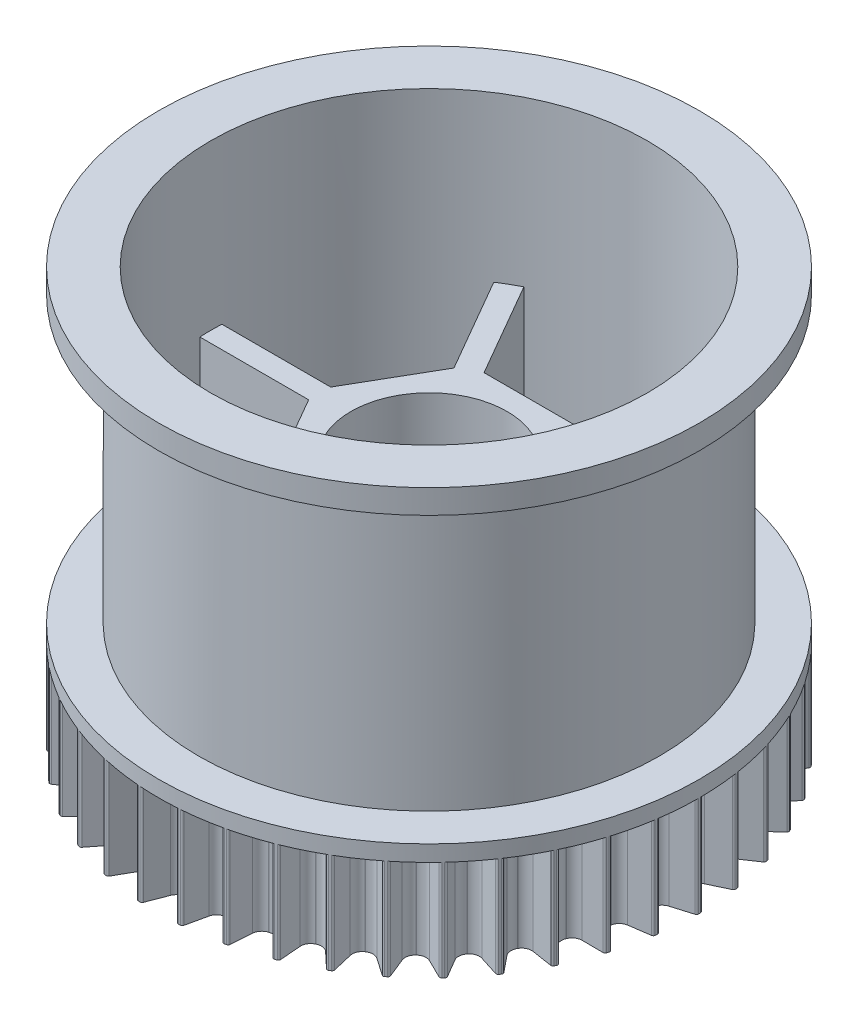
SolidWorks part; units mm, degrees
ref_plane "前视基准面" through (0, 0, 0) normal (0, 0, 1) x (1, 0, 0)
ref_plane "上视基准面" through (0, 0, 0) normal (0, 1, 0) x (1, 0, 0)
ref_plane "右视基准面" through (0, 0, 0) normal (1, 0, 0) x (0, 0, -1)
other "Configuration Table"
sketch "草图1" plane through (0, 0, 0) normal (0, 1, 0) x (1, 0, 0)
  line L0 (0, 0) -> (7.9279, 0) construction
  line L1 (0, 0) -> (0, 4.4256) construction
  line L2 (12.4216, 0.4494) -> (13.4287, 0.1463)
  line L3 (12.4216, -0.4494) -> (13.4287, -0.1463)
  line L4 (12.2159, -2.2957) -> (13.2569, -2.1461)
  line L5 (12.3499, -1.407) -> (13.3005, -1.8568)
  line L6 (11.7373, -4.0908) -> (12.789, -4.098)
  line L7 (12.0023, -3.2319) -> (12.8752, -3.8184)
  line L8 (10.9965, -5.7945) -> (12.0354, -5.9583)
  line L9 (11.3865, -4.9846) -> (12.1623, -5.6947)
  line L10 (10.0101, -7.3687) -> (11.0129, -7.6855)
  line L11 (10.5164, -6.626) -> (11.1777, -7.4438)
  line L12 (8.8, -8.7783) -> (9.7445, -9.2411)
  line L13 (9.4114, -8.1194) -> (9.9434, -9.0266)
  line L14 (7.3934, -9.9918) -> (8.2583, -10.5902)
  line L15 (8.0961, -9.4314) -> (8.487, -10.4078)
  line L16 (5.8216, -10.9822) -> (6.5877, -11.7028)
  line L17 (6.6, -10.5328) -> (6.841, -11.5565)
  line L18 (4.1198, -11.7272) -> (4.7699, -12.5539)
  line L19 (4.9565, -11.3988) -> (5.0422, -12.447)
  line L20 (2.3259, -12.2102) -> (2.8456, -13.1246)
  line L21 (3.2022, -12.0102) -> (3.1308, -13.0595)
  line L22 (0.4801, -12.4205) -> (0.8577, -13.4021)
  line L23 (1.3764, -12.3533) -> (1.1494, -13.3802)
  line L24 (-1.3764, -12.3533) -> (-1.1494, -13.3802)
  line L25 (-0.4801, -12.4205) -> (-0.8577, -13.4021)
  line L26 (-3.2022, -12.0102) -> (-3.1308, -13.0595)
  line L27 (-2.3259, -12.2102) -> (-2.8456, -13.1246)
  line L28 (-4.9565, -11.3988) -> (-5.0422, -12.447)
  line L29 (-4.1198, -11.7272) -> (-4.7699, -12.5539)
  line L30 (-6.6, -10.5328) -> (-6.841, -11.5565)
  line L31 (-5.8216, -10.9822) -> (-6.5877, -11.7028)
  line L32 (-8.0961, -9.4314) -> (-8.487, -10.4078)
  line L33 (-7.3934, -9.9918) -> (-8.2583, -10.5902)
  line L34 (-9.4114, -8.1194) -> (-9.9434, -9.0266)
  line L35 (-8.8, -8.7783) -> (-9.7445, -9.2411)
  line L36 (-10.5164, -6.626) -> (-11.1777, -7.4438)
  line L37 (-10.0101, -7.3687) -> (-11.0129, -7.6855)
  line L38 (-11.3865, -4.9846) -> (-12.1623, -5.6947)
  line L39 (-10.9965, -5.7945) -> (-12.0354, -5.9583)
  line L40 (-12.0023, -3.2319) -> (-12.8752, -3.8184)
  line L41 (-11.7373, -4.0908) -> (-12.789, -4.098)
  line L42 (-12.3499, -1.407) -> (-13.3005, -1.8568)
  line L43 (-12.2159, -2.2957) -> (-13.2569, -2.1461)
  line L44 (-12.4216, 0.4494) -> (-13.4287, 0.1463)
  line L45 (-12.4216, -0.4494) -> (-13.4287, -0.1463)
  line L46 (-12.2159, 2.2957) -> (-13.2569, 2.1461)
  line L47 (-12.3499, 1.407) -> (-13.3005, 1.8568)
  line L48 (-11.7373, 4.0908) -> (-12.789, 4.098)
  line L49 (-12.0023, 3.2319) -> (-12.8752, 3.8184)
  line L50 (-10.9965, 5.7945) -> (-12.0354, 5.9583)
  line L51 (-11.3865, 4.9846) -> (-12.1623, 5.6947)
  line L52 (-10.0101, 7.3687) -> (-11.0129, 7.6855)
  line L53 (-10.5164, 6.626) -> (-11.1777, 7.4438)
  line L54 (-8.8, 8.7783) -> (-9.7445, 9.2411)
  line L55 (-9.4114, 8.1194) -> (-9.9434, 9.0266)
  line L56 (-7.3934, 9.9918) -> (-8.2583, 10.5902)
  line L57 (-8.0961, 9.4314) -> (-8.487, 10.4078)
  line L58 (-5.8216, 10.9822) -> (-6.5877, 11.7028)
  line L59 (-6.6, 10.5328) -> (-6.841, 11.5565)
  line L60 (-4.1198, 11.7272) -> (-4.7699, 12.5539)
  line L61 (-4.9565, 11.3988) -> (-5.0422, 12.447)
  line L62 (-2.3259, 12.2102) -> (-2.8456, 13.1246)
  line L63 (-3.2022, 12.0102) -> (-3.1308, 13.0595)
  line L64 (-0.4801, 12.4205) -> (-0.8577, 13.4021)
  line L65 (-1.3764, 12.3533) -> (-1.1494, 13.3802)
  line L66 (1.3764, 12.3533) -> (1.1494, 13.3802)
  line L67 (0.4801, 12.4205) -> (0.8577, 13.4021)
  line L68 (3.2022, 12.0102) -> (3.1308, 13.0595)
  line L69 (2.3259, 12.2102) -> (2.8456, 13.1246)
  line L70 (4.9565, 11.3988) -> (5.0422, 12.447)
  line L71 (4.1198, 11.7272) -> (4.7699, 12.5539)
  line L72 (6.6, 10.5328) -> (6.841, 11.5565)
  line L73 (5.8216, 10.9822) -> (6.5877, 11.7028)
  line L74 (8.0961, 9.4314) -> (8.487, 10.4078)
  line L75 (7.3934, 9.9918) -> (8.2583, 10.5902)
  line L76 (9.4114, 8.1194) -> (9.9434, 9.0266)
  line L77 (8.8, 8.7783) -> (9.7445, 9.2411)
  line L78 (10.5164, 6.626) -> (11.1777, 7.4438)
  line L79 (10.0101, 7.3687) -> (11.0129, 7.6855)
  line L80 (11.3865, 4.9846) -> (12.1623, 5.6947)
  line L81 (10.9965, 5.7945) -> (12.0354, 5.9583)
  line L82 (12.0023, 3.2319) -> (12.8752, 3.8184)
  line L83 (11.7373, 4.0908) -> (12.789, 4.098)
  line L84 (12.3499, 1.407) -> (13.3005, 1.8568)
  line L85 (12.2159, 2.2957) -> (13.2569, 2.1461)
  line L95 (2.8868, 5) -> (-2.8868, 5) construction
  line L96 (2.8868, 5) -> (5.456, 0.55) construction
  line L97 (0, 0) -> (2.8868, 5) construction
  line L98 (-2.8868, 5) -> (-5.456, 0.55) construction
  line L99 (3.2043, -4.45) -> (5.456, -0.55)
  line L100 (2.2517, -5) -> (-2.2517, -5)
  line L101 (-3.2043, -4.45) -> (-5.456, -0.55)
  line L102 (8.1752, 0) -> (11.2, 0) construction
  line L103 (5.456, 0.55) -> (11.1865, 0.55)
  line L104 (5.456, -0.55) -> (11.1865, -0.55)
  line L105 (3.2043, -4.45) -> (6.0696, -9.4128)
  line L106 (2.2517, -5) -> (5.1169, -9.9628)
  line L107 (-2.2517, -5) -> (-5.1169, -9.9628)
  line L108 (-3.2043, -4.45) -> (-6.0696, -9.4128)
  line L109 (-5.456, -0.55) -> (-11.1865, -0.55)
  line L110 (-5.456, 0.55) -> (-11.1865, 0.55)
  line L111 (-3.2043, 4.45) -> (-6.0696, 9.4128)
  line L112 (-2.2517, 5) -> (-5.1169, 9.9628)
  line L113 (2.2517, 5) -> (5.1169, 9.9628)
  line L114 (3.2043, 4.45) -> (6.0696, 9.4128)
  line L115 (0, 0) -> (12.0337, 1.2648) construction
  line L116 (12.0337, -1.2648) -> (0, 0) construction
  line L117 (-5.456, 0.55) -> (-3.2043, 4.45)
  line L118 (-2.2517, 5) -> (2.2517, 5)
  line L119 (3.2043, 4.45) -> (5.456, 0.55)
  circle A0 centre (0, 0) radius 11.2 construction
  circle A1 centre (0, 0) radius 12.1 construction
  circle A2 centre (0, 0) radius 13.5 construction
  arc A3 (13.4999, 0.0509) -> (13.4999, -0.0509) centre (0, 0) cw
  arc A4 (12.0671, 0.8914) -> (12.0337, 1.2648) centre (0, 0) ccw construction
  arc A5 (13.4287, -0.1463) -> (13.4999, -0.0509) centre (13.3999, -0.0505) ccw
  arc A6 (13.4287, 0.1463) -> (13.4999, 0.0509) centre (13.3999, 0.0505) cw
  arc A7 (12.0671, -0.8914) -> (12.0337, -1.2648) centre (0, 0) cw construction
  arc A8 (12.4216, -0.4494) -> (12.0671, -0.8914) centre (12.5658, -0.9282) ccw
  arc A9 (12.4216, 0.4494) -> (12.0671, 0.8914) centre (12.5658, 0.9282) cw
  arc A10 (12.2159, -2.2957) -> (11.7995, -2.6799) centre (12.2871, -2.7907) ccw
  arc A11 (12.3499, -1.407) -> (12.0652, -0.9171) centre (12.5638, -0.955) cw
  arc A12 (13.3005, -1.8568) -> (13.3567, -1.9617) centre (13.2578, -1.9472) cw
  arc A13 (13.3567, -1.9617) -> (13.3415, -2.0624) centre (0, 0) cw
  arc A14 (13.2569, -2.1461) -> (13.3415, -2.0624) centre (13.2427, -2.0471) ccw
  arc A15 (11.7373, -4.0908) -> (11.2683, -4.4086) centre (11.7339, -4.5908) ccw
  arc A16 (12.0023, -3.2319) -> (11.7937, -2.7051) centre (12.2811, -2.8169) cw
  arc A17 (12.8752, -3.8184) -> (12.9151, -3.9305) centre (12.8195, -3.9014) cw
  arc A18 (12.9151, -3.9305) -> (12.8851, -4.0278) centre (0, 0) cw
  arc A19 (12.789, -4.098) -> (12.8851, -4.0278) centre (12.7897, -3.998) ccw
  arc A20 (10.9965, -5.7945) -> (10.4854, -6.0388) centre (10.9186, -6.2884) ccw
  arc A21 (11.3865, -4.9846) -> (11.2589, -4.4326) centre (11.7241, -4.6158) cw
  arc A22 (12.1623, -5.6947) -> (12.1851, -5.8115) centre (12.0948, -5.7685) cw
  arc A23 (12.1851, -5.8115) -> (12.1409, -5.9032) centre (0, 0) cw
  arc A24 (12.0354, -5.9583) -> (12.1409, -5.9032) centre (12.051, -5.8595) ccw
  arc A25 (10.0101, -7.3687) -> (9.4682, -7.5341) centre (9.8595, -7.8455) ccw
  arc A26 (10.5164, -6.626) -> (10.4724, -6.0612) centre (10.9052, -6.3116) cw
  arc A27 (11.1777, -7.4438) -> (11.1828, -7.5627) centre (11.1, -7.5067) cw
  arc A28 (11.1828, -7.5627) -> (11.1255, -7.6468) centre (0, 0) cw
  arc A29 (11.0129, -7.6855) -> (11.1255, -7.6468) centre (11.0431, -7.5902) ccw
  arc A30 (8.8, -8.7783) -> (8.2395, -8.8611) centre (8.58, -9.2273) ccw
  arc A31 (9.4114, -8.1194) -> (9.4521, -7.5543) centre (9.8427, -7.8665) cw
  arc A32 (9.9434, -9.0266) -> (9.9308, -9.145) centre (9.8572, -9.0772) cw
  arc A33 (9.9308, -9.145) -> (9.8615, -9.2196) centre (0, 0) cw
  arc A34 (9.7445, -9.2411) -> (9.8615, -9.2196) centre (9.7885, -9.1513) ccw
  arc A35 (7.3934, -9.9918) -> (6.8268, -9.9902) centre (7.1089, -10.403) ccw
  arc A36 (8.0961, -9.4314) -> (8.2206, -8.8787) centre (8.5603, -9.2456) cw
  arc A37 (8.487, -10.4078) -> (8.4568, -10.5229) centre (8.3942, -10.445) cw
  arc A38 (8.4568, -10.5229) -> (8.3773, -10.5864) centre (0, 0) cw
  arc A39 (8.2583, -10.5902) -> (8.3773, -10.5864) centre (8.3152, -10.508) ccw
  arc A40 (5.8216, -10.9822) -> (5.2616, -10.8961) centre (5.479, -11.3464) ccw
  arc A41 (6.6, -10.5328) -> (6.8055, -10.0048) centre (7.0867, -10.4182) cw
  arc A42 (6.841, -11.5565) -> (6.794, -11.6658) centre (6.7437, -11.5794) cw
  arc A43 (6.794, -11.6658) -> (6.7059, -11.7167) centre (0, 0) cw
  arc A44 (6.5877, -11.7028) -> (6.7059, -11.7167) centre (6.6562, -11.6299) ccw
  arc A45 (4.1198, -11.7272) -> (3.5789, -11.5586) centre (3.7268, -12.0362) ccw
  arc A46 (4.9565, -11.3988) -> (5.2384, -10.9073) centre (5.4548, -11.358) cw
  arc A47 (5.0422, -12.447) -> (4.9795, -12.5481) centre (4.9426, -12.4552) cw
  arc A48 (4.9795, -12.5481) -> (4.8847, -12.5853) centre (0, 0) cw
  arc A49 (4.7699, -12.5539) -> (4.8847, -12.5853) centre (4.8485, -12.4921) ccw
  arc A50 (2.3259, -12.2102) -> (1.8162, -11.9629) centre (1.8912, -12.4573) ccw
  arc A51 (3.2022, -12.0102) -> (3.5542, -11.5662) centre (3.7011, -12.0442) cw
  arc A52 (3.1308, -13.0595) -> (3.0536, -13.1501) centre (3.031, -13.0527) cw
  arc A53 (3.0536, -13.1501) -> (2.9544, -13.1728) centre (0, 0) cw
  arc A54 (2.8456, -13.1246) -> (2.9544, -13.1728) centre (2.9325, -13.0752) ccw
  arc A55 (0.4801, -12.4205) -> (0.0129, -12.1) centre (0.0134, -12.6) ccw
  arc A56 (1.3764, -12.3533) -> (1.7906, -11.9668) centre (1.8646, -12.4613) cw
  arc A57 (1.1494, -13.3802) -> (1.0596, -13.4584) centre (1.0518, -13.3587) cw
  arc A58 (1.0596, -13.4584) -> (0.9581, -13.466) centre (0, 0) cw
  arc A59 (0.8577, -13.4021) -> (0.9581, -13.466) centre (0.951, -13.3662) ccw
  arc A60 (-1.3764, -12.3533) -> (-1.7906, -11.9668) centre (-1.8646, -12.4613) ccw
  arc A61 (-0.4801, -12.4205) -> (-0.0129, -12.1) centre (-0.0134, -12.6) cw
  arc A62 (-0.8577, -13.4021) -> (-0.9581, -13.466) centre (-0.951, -13.3662) cw
  arc A63 (-0.9581, -13.466) -> (-1.0596, -13.4584) centre (0, 0) cw
  arc A64 (-1.1494, -13.3802) -> (-1.0596, -13.4584) centre (-1.0518, -13.3587) ccw
  arc A65 (-3.2022, -12.0102) -> (-3.5542, -11.5662) centre (-3.7011, -12.0442) ccw
  arc A66 (-2.3259, -12.2102) -> (-1.8162, -11.9629) centre (-1.8912, -12.4573) cw
  arc A67 (-2.8456, -13.1246) -> (-2.9544, -13.1728) centre (-2.9325, -13.0752) cw
  arc A68 (-2.9544, -13.1728) -> (-3.0536, -13.1501) centre (0, 0) cw
  arc A69 (-3.1308, -13.0595) -> (-3.0536, -13.1501) centre (-3.031, -13.0527) ccw
  arc A70 (-4.9565, -11.3988) -> (-5.2384, -10.9073) centre (-5.4548, -11.358) ccw
  arc A71 (-4.1198, -11.7272) -> (-3.5789, -11.5586) centre (-3.7268, -12.0362) cw
  arc A72 (-4.7699, -12.5539) -> (-4.8847, -12.5853) centre (-4.8485, -12.4921) cw
  arc A73 (-4.8847, -12.5853) -> (-4.9795, -12.5481) centre (0, 0) cw
  arc A74 (-5.0422, -12.447) -> (-4.9795, -12.5481) centre (-4.9426, -12.4552) ccw
  arc A75 (-6.6, -10.5328) -> (-6.8055, -10.0048) centre (-7.0867, -10.4182) ccw
  arc A76 (-5.8216, -10.9822) -> (-5.2616, -10.8961) centre (-5.479, -11.3464) cw
  arc A77 (-6.5877, -11.7028) -> (-6.7059, -11.7167) centre (-6.6562, -11.6299) cw
  arc A78 (-6.7059, -11.7167) -> (-6.794, -11.6658) centre (0, 0) cw
  arc A79 (-6.841, -11.5565) -> (-6.794, -11.6658) centre (-6.7437, -11.5794) ccw
  arc A80 (-8.0961, -9.4314) -> (-8.2206, -8.8787) centre (-8.5603, -9.2456) ccw
  arc A81 (-7.3934, -9.9918) -> (-6.8268, -9.9902) centre (-7.1089, -10.403) cw
  arc A82 (-8.2583, -10.5902) -> (-8.3773, -10.5864) centre (-8.3152, -10.508) cw
  arc A83 (-8.3773, -10.5864) -> (-8.4568, -10.5229) centre (0, 0) cw
  arc A84 (-8.487, -10.4078) -> (-8.4568, -10.5229) centre (-8.3942, -10.445) ccw
  arc A85 (-9.4114, -8.1194) -> (-9.4521, -7.5543) centre (-9.8427, -7.8665) ccw
  arc A86 (-8.8, -8.7783) -> (-8.2395, -8.8611) centre (-8.58, -9.2273) cw
  arc A87 (-9.7445, -9.2411) -> (-9.8615, -9.2196) centre (-9.7885, -9.1513) cw
  arc A88 (-9.8615, -9.2196) -> (-9.9308, -9.145) centre (0, 0) cw
  arc A89 (-9.9434, -9.0266) -> (-9.9308, -9.145) centre (-9.8572, -9.0772) ccw
  arc A90 (-10.5164, -6.626) -> (-10.4724, -6.0612) centre (-10.9052, -6.3116) ccw
  arc A91 (-10.0101, -7.3687) -> (-9.4682, -7.5341) centre (-9.8595, -7.8455) cw
  arc A92 (-11.0129, -7.6855) -> (-11.1255, -7.6468) centre (-11.0431, -7.5902) cw
  arc A93 (-11.1255, -7.6468) -> (-11.1828, -7.5627) centre (0, 0) cw
  arc A94 (-11.1777, -7.4438) -> (-11.1828, -7.5627) centre (-11.1, -7.5067) ccw
  arc A95 (-11.3865, -4.9846) -> (-11.2589, -4.4326) centre (-11.7241, -4.6158) ccw
  arc A96 (-10.9965, -5.7945) -> (-10.4854, -6.0388) centre (-10.9186, -6.2884) cw
  arc A97 (-12.0354, -5.9583) -> (-12.1409, -5.9032) centre (-12.051, -5.8595) cw
  arc A98 (-12.1409, -5.9032) -> (-12.1851, -5.8115) centre (0, 0) cw
  arc A99 (-12.1623, -5.6947) -> (-12.1851, -5.8115) centre (-12.0948, -5.7685) ccw
  arc A100 (-12.0023, -3.2319) -> (-11.7937, -2.7051) centre (-12.2811, -2.8169) ccw
  arc A101 (-11.7373, -4.0908) -> (-11.2683, -4.4086) centre (-11.7339, -4.5908) cw
  arc A102 (-12.789, -4.098) -> (-12.8851, -4.0278) centre (-12.7897, -3.998) cw
  arc A103 (-12.8851, -4.0278) -> (-12.9151, -3.9305) centre (0, 0) cw
  arc A104 (-12.8752, -3.8184) -> (-12.9151, -3.9305) centre (-12.8195, -3.9014) ccw
  arc A105 (-12.3499, -1.407) -> (-12.0652, -0.9171) centre (-12.5638, -0.955) ccw
  arc A106 (-12.2159, -2.2957) -> (-11.7995, -2.6799) centre (-12.2871, -2.7907) cw
  arc A107 (-13.2569, -2.1461) -> (-13.3415, -2.0624) centre (-13.2427, -2.0471) cw
  arc A108 (-13.3415, -2.0624) -> (-13.3567, -1.9617) centre (0, 0) cw
  arc A109 (-13.3005, -1.8568) -> (-13.3567, -1.9617) centre (-13.2578, -1.9472) ccw
  arc A110 (-12.4216, 0.4494) -> (-12.0671, 0.8914) centre (-12.5658, 0.9282) ccw
  arc A111 (-12.4216, -0.4494) -> (-12.0671, -0.8914) centre (-12.5658, -0.9282) cw
  arc A112 (-13.4287, -0.1463) -> (-13.4999, -0.0509) centre (-13.3999, -0.0505) cw
  arc A113 (-13.4999, -0.0509) -> (-13.4999, 0.0509) centre (0, 0) cw
  arc A114 (-13.4287, 0.1463) -> (-13.4999, 0.0509) centre (-13.3999, 0.0505) ccw
  arc A115 (-12.2159, 2.2957) -> (-11.7995, 2.6799) centre (-12.2871, 2.7907) ccw
  arc A116 (-12.3499, 1.407) -> (-12.0652, 0.9171) centre (-12.5638, 0.955) cw
  arc A117 (-13.3005, 1.8568) -> (-13.3567, 1.9617) centre (-13.2578, 1.9472) cw
  arc A118 (-13.3567, 1.9617) -> (-13.3415, 2.0624) centre (0, 0) cw
  arc A119 (-13.2569, 2.1461) -> (-13.3415, 2.0624) centre (-13.2427, 2.0471) ccw
  arc A120 (-11.7373, 4.0908) -> (-11.2683, 4.4086) centre (-11.7339, 4.5908) ccw
  arc A121 (-12.0023, 3.2319) -> (-11.7937, 2.7051) centre (-12.2811, 2.8169) cw
  arc A122 (-12.8752, 3.8184) -> (-12.9151, 3.9305) centre (-12.8195, 3.9014) cw
  arc A123 (-12.9151, 3.9305) -> (-12.8851, 4.0278) centre (0, 0) cw
  arc A124 (-12.789, 4.098) -> (-12.8851, 4.0278) centre (-12.7897, 3.998) ccw
  arc A125 (-10.9965, 5.7945) -> (-10.4854, 6.0388) centre (-10.9186, 6.2884) ccw
  arc A126 (-11.3865, 4.9846) -> (-11.2589, 4.4326) centre (-11.7241, 4.6158) cw
  arc A127 (-12.1623, 5.6947) -> (-12.1851, 5.8115) centre (-12.0948, 5.7685) cw
  arc A128 (-12.1851, 5.8115) -> (-12.1409, 5.9032) centre (0, 0) cw
  arc A129 (-12.0354, 5.9583) -> (-12.1409, 5.9032) centre (-12.051, 5.8595) ccw
  arc A130 (-10.0101, 7.3687) -> (-9.4682, 7.5341) centre (-9.8595, 7.8455) ccw
  arc A131 (-10.5164, 6.626) -> (-10.4724, 6.0612) centre (-10.9052, 6.3116) cw
  arc A132 (-11.1777, 7.4438) -> (-11.1828, 7.5627) centre (-11.1, 7.5067) cw
  arc A133 (-11.1828, 7.5627) -> (-11.1255, 7.6468) centre (0, 0) cw
  arc A134 (-11.0129, 7.6855) -> (-11.1255, 7.6468) centre (-11.0431, 7.5902) ccw
  arc A135 (-8.8, 8.7783) -> (-8.2395, 8.8611) centre (-8.58, 9.2273) ccw
  arc A136 (-9.4114, 8.1194) -> (-9.4521, 7.5543) centre (-9.8427, 7.8665) cw
  arc A137 (-9.9434, 9.0266) -> (-9.9308, 9.145) centre (-9.8572, 9.0772) cw
  arc A138 (-9.9308, 9.145) -> (-9.8615, 9.2196) centre (0, 0) cw
  arc A139 (-9.7445, 9.2411) -> (-9.8615, 9.2196) centre (-9.7885, 9.1513) ccw
  arc A140 (-7.3934, 9.9918) -> (-6.8268, 9.9902) centre (-7.1089, 10.403) ccw
  arc A141 (-8.0961, 9.4314) -> (-8.2206, 8.8787) centre (-8.5603, 9.2456) cw
  arc A142 (-8.487, 10.4078) -> (-8.4568, 10.5229) centre (-8.3942, 10.445) cw
  arc A143 (-8.4568, 10.5229) -> (-8.3773, 10.5864) centre (0, 0) cw
  arc A144 (-8.2583, 10.5902) -> (-8.3773, 10.5864) centre (-8.3152, 10.508) ccw
  arc A145 (-5.8216, 10.9822) -> (-5.2616, 10.8961) centre (-5.479, 11.3464) ccw
  arc A146 (-6.6, 10.5328) -> (-6.8055, 10.0048) centre (-7.0867, 10.4182) cw
  arc A147 (-6.841, 11.5565) -> (-6.794, 11.6658) centre (-6.7437, 11.5794) cw
  arc A148 (-6.794, 11.6658) -> (-6.7059, 11.7167) centre (0, 0) cw
  arc A149 (-6.5877, 11.7028) -> (-6.7059, 11.7167) centre (-6.6562, 11.6299) ccw
  arc A150 (-4.1198, 11.7272) -> (-3.5789, 11.5586) centre (-3.7268, 12.0362) ccw
  arc A151 (-4.9565, 11.3988) -> (-5.2384, 10.9073) centre (-5.4548, 11.358) cw
  arc A152 (-5.0422, 12.447) -> (-4.9795, 12.5481) centre (-4.9426, 12.4552) cw
  arc A153 (-4.9795, 12.5481) -> (-4.8847, 12.5853) centre (0, 0) cw
  arc A154 (-4.7699, 12.5539) -> (-4.8847, 12.5853) centre (-4.8485, 12.4921) ccw
  arc A155 (-2.3259, 12.2102) -> (-1.8162, 11.9629) centre (-1.8912, 12.4573) ccw
  arc A156 (-3.2022, 12.0102) -> (-3.5542, 11.5662) centre (-3.7011, 12.0442) cw
  arc A157 (-3.1308, 13.0595) -> (-3.0536, 13.1501) centre (-3.031, 13.0527) cw
  arc A158 (-3.0536, 13.1501) -> (-2.9544, 13.1728) centre (0, 0) cw
  arc A159 (-2.8456, 13.1246) -> (-2.9544, 13.1728) centre (-2.9325, 13.0752) ccw
  arc A160 (-0.4801, 12.4205) -> (-0.0129, 12.1) centre (-0.0134, 12.6) ccw
  arc A161 (-1.3764, 12.3533) -> (-1.7906, 11.9668) centre (-1.8646, 12.4613) cw
  arc A162 (-1.1494, 13.3802) -> (-1.0596, 13.4584) centre (-1.0518, 13.3587) cw
  arc A163 (-1.0596, 13.4584) -> (-0.9581, 13.466) centre (0, 0) cw
  arc A164 (-0.8577, 13.4021) -> (-0.9581, 13.466) centre (-0.951, 13.3662) ccw
  arc A165 (1.3764, 12.3533) -> (1.7906, 11.9668) centre (1.8646, 12.4613) ccw
  arc A166 (0.4801, 12.4205) -> (0.0129, 12.1) centre (0.0134, 12.6) cw
  arc A167 (0.8577, 13.4021) -> (0.9581, 13.466) centre (0.951, 13.3662) cw
  arc A168 (0.9581, 13.466) -> (1.0596, 13.4584) centre (0, 0) cw
  arc A169 (1.1494, 13.3802) -> (1.0596, 13.4584) centre (1.0518, 13.3587) ccw
  arc A170 (3.2022, 12.0102) -> (3.5542, 11.5662) centre (3.7011, 12.0442) ccw
  arc A171 (2.3259, 12.2102) -> (1.8162, 11.9629) centre (1.8912, 12.4573) cw
  arc A172 (2.8456, 13.1246) -> (2.9544, 13.1728) centre (2.9325, 13.0752) cw
  arc A173 (2.9544, 13.1728) -> (3.0536, 13.1501) centre (0, 0) cw
  arc A174 (3.1308, 13.0595) -> (3.0536, 13.1501) centre (3.031, 13.0527) ccw
  arc A175 (4.9565, 11.3988) -> (5.2384, 10.9073) centre (5.4548, 11.358) ccw
  arc A176 (4.1198, 11.7272) -> (3.5789, 11.5586) centre (3.7268, 12.0362) cw
  arc A177 (4.7699, 12.5539) -> (4.8847, 12.5853) centre (4.8485, 12.4921) cw
  arc A178 (4.8847, 12.5853) -> (4.9795, 12.5481) centre (0, 0) cw
  arc A179 (5.0422, 12.447) -> (4.9795, 12.5481) centre (4.9426, 12.4552) ccw
  arc A180 (6.6, 10.5328) -> (6.8055, 10.0048) centre (7.0867, 10.4182) ccw
  arc A181 (5.8216, 10.9822) -> (5.2616, 10.8961) centre (5.479, 11.3464) cw
  arc A182 (6.5877, 11.7028) -> (6.7059, 11.7167) centre (6.6562, 11.6299) cw
  arc A183 (6.7059, 11.7167) -> (6.794, 11.6658) centre (0, 0) cw
  arc A184 (6.841, 11.5565) -> (6.794, 11.6658) centre (6.7437, 11.5794) ccw
  arc A185 (8.0961, 9.4314) -> (8.2206, 8.8787) centre (8.5603, 9.2456) ccw
  arc A186 (7.3934, 9.9918) -> (6.8268, 9.9902) centre (7.1089, 10.403) cw
  arc A187 (8.2583, 10.5902) -> (8.3773, 10.5864) centre (8.3152, 10.508) cw
  arc A188 (8.3773, 10.5864) -> (8.4568, 10.5229) centre (0, 0) cw
  arc A189 (8.487, 10.4078) -> (8.4568, 10.5229) centre (8.3942, 10.445) ccw
  arc A190 (9.4114, 8.1194) -> (9.4521, 7.5543) centre (9.8427, 7.8665) ccw
  arc A191 (8.8, 8.7783) -> (8.2395, 8.8611) centre (8.58, 9.2273) cw
  arc A192 (9.7445, 9.2411) -> (9.8615, 9.2196) centre (9.7885, 9.1513) cw
  arc A193 (9.8615, 9.2196) -> (9.9308, 9.145) centre (0, 0) cw
  arc A194 (9.9434, 9.0266) -> (9.9308, 9.145) centre (9.8572, 9.0772) ccw
  arc A195 (10.5164, 6.626) -> (10.4724, 6.0612) centre (10.9052, 6.3116) ccw
  arc A196 (10.0101, 7.3687) -> (9.4682, 7.5341) centre (9.8595, 7.8455) cw
  arc A197 (11.0129, 7.6855) -> (11.1255, 7.6468) centre (11.0431, 7.5902) cw
  arc A198 (11.1255, 7.6468) -> (11.1828, 7.5627) centre (0, 0) cw
  arc A199 (11.1777, 7.4438) -> (11.1828, 7.5627) centre (11.1, 7.5067) ccw
  arc A200 (11.3865, 4.9846) -> (11.2589, 4.4326) centre (11.7241, 4.6158) ccw
  arc A201 (10.9965, 5.7945) -> (10.4854, 6.0388) centre (10.9186, 6.2884) cw
  arc A202 (12.0354, 5.9583) -> (12.1409, 5.9032) centre (12.051, 5.8595) cw
  arc A203 (12.1409, 5.9032) -> (12.1851, 5.8115) centre (0, 0) cw
  arc A204 (12.1623, 5.6947) -> (12.1851, 5.8115) centre (12.0948, 5.7685) ccw
  arc A205 (12.0023, 3.2319) -> (11.7937, 2.7051) centre (12.2811, 2.8169) ccw
  arc A206 (11.7373, 4.0908) -> (11.2683, 4.4086) centre (11.7339, 4.5908) cw
  arc A207 (12.789, 4.098) -> (12.8851, 4.0278) centre (12.7897, 3.998) cw
  arc A208 (12.8851, 4.0278) -> (12.9151, 3.9305) centre (0, 0) cw
  arc A209 (12.8752, 3.8184) -> (12.9151, 3.9305) centre (12.8195, 3.9014) ccw
  arc A210 (12.3499, 1.407) -> (12.0652, 0.9171) centre (12.5638, 0.955) ccw
  arc A211 (12.2159, 2.2957) -> (11.7995, 2.6799) centre (12.2871, 2.7907) cw
  arc A212 (13.2569, 2.1461) -> (13.3415, 2.0624) centre (13.2427, 2.0471) cw
  arc A213 (13.3415, 2.0624) -> (13.3567, 1.9617) centre (0, 0) cw
  arc A214 (13.3005, 1.8568) -> (13.3567, 1.9617) centre (13.2578, 1.9472) ccw
  circle A216 centre (0, 0) radius 3.9
  arc A217 (11.1865, 0.55) -> (6.0696, 9.4128) centre (0, 0) ccw
  arc A218 (5.1169, 9.9628) -> (-5.1169, 9.9628) centre (0, 0) ccw
  arc A219 (-6.0696, 9.4128) -> (-11.1865, 0.55) centre (0, 0) ccw
  arc A220 (-11.1865, -0.55) -> (-6.0696, -9.4128) centre (0, 0) ccw
  arc A221 (-5.1169, -9.9628) -> (5.1169, -9.9628) centre (0, 0) ccw
  arc A222 (6.0696, -9.4128) -> (11.1865, -0.55) centre (0, 0) ccw
  arc A223 (12.0652, 0.9171) -> (12.0671, 0.8914) centre (0, 0) cw
  arc A224 (12.0671, -0.8914) -> (12.0652, -0.9171) centre (0, 0) cw
  arc A225 (11.7995, -2.6799) -> (11.7937, -2.7051) centre (0, 0) cw
  arc A226 (11.2683, -4.4086) -> (11.2589, -4.4326) centre (0, 0) cw
  arc A227 (10.4854, -6.0388) -> (10.4724, -6.0612) centre (0, 0) cw
  arc A228 (9.4682, -7.5341) -> (9.4521, -7.5543) centre (0, 0) cw
  arc A229 (8.2395, -8.8611) -> (8.2206, -8.8787) centre (0, 0) cw
  arc A230 (6.8268, -9.9902) -> (6.8055, -10.0048) centre (0, 0) cw
  arc A231 (5.2616, -10.8961) -> (5.2384, -10.9073) centre (0, 0) cw
  arc A232 (3.5789, -11.5586) -> (3.5542, -11.5662) centre (0, 0) cw
  arc A233 (1.8162, -11.9629) -> (1.7906, -11.9668) centre (0, 0) cw
  arc A234 (0.0129, -12.1) -> (-0.0129, -12.1) centre (0, 0) cw
  arc A235 (-1.7906, -11.9668) -> (-1.8162, -11.9629) centre (0, 0) cw
  arc A236 (-3.5542, -11.5662) -> (-3.5789, -11.5586) centre (0, 0) cw
  arc A237 (-5.2384, -10.9073) -> (-5.2616, -10.8961) centre (0, 0) cw
  arc A238 (-6.8055, -10.0048) -> (-6.8268, -9.9902) centre (0, 0) cw
  arc A239 (-8.2206, -8.8787) -> (-8.2395, -8.8611) centre (0, 0) cw
  arc A240 (-9.4521, -7.5543) -> (-9.4682, -7.5341) centre (0, 0) cw
  arc A241 (-10.4724, -6.0612) -> (-10.4854, -6.0388) centre (0, 0) cw
  arc A242 (-11.2589, -4.4326) -> (-11.2683, -4.4086) centre (0, 0) cw
  arc A243 (-11.7937, -2.7051) -> (-11.7995, -2.6799) centre (0, 0) cw
  arc A244 (-12.0652, -0.9171) -> (-12.0671, -0.8914) centre (0, 0) cw
  arc A245 (-12.0671, 0.8914) -> (-12.0652, 0.9171) centre (0, 0) cw
  arc A246 (-11.7995, 2.6799) -> (-11.7937, 2.7051) centre (0, 0) cw
  arc A247 (-11.2683, 4.4086) -> (-11.2589, 4.4326) centre (0, 0) cw
  arc A248 (-10.4854, 6.0388) -> (-10.4724, 6.0612) centre (0, 0) cw
  arc A249 (-9.4682, 7.5341) -> (-9.4521, 7.5543) centre (0, 0) cw
  arc A250 (-8.2395, 8.8611) -> (-8.2206, 8.8787) centre (0, 0) cw
  arc A251 (-6.8268, 9.9902) -> (-6.8055, 10.0048) centre (0, 0) cw
  arc A252 (-5.2616, 10.8961) -> (-5.2384, 10.9073) centre (0, 0) cw
  arc A253 (-3.5789, 11.5586) -> (-3.5542, 11.5662) centre (0, 0) cw
  arc A254 (-1.8162, 11.9629) -> (-1.7906, 11.9668) centre (0, 0) cw
  arc A255 (-0.0129, 12.1) -> (0.0129, 12.1) centre (0, 0) cw
  arc A256 (1.7906, 11.9668) -> (1.8162, 11.9629) centre (0, 0) cw
  arc A257 (3.5542, 11.5662) -> (3.5789, 11.5586) centre (0, 0) cw
  arc A258 (5.2384, 10.9073) -> (5.2616, 10.8961) centre (0, 0) cw
  arc A259 (6.8055, 10.0048) -> (6.8268, 9.9902) centre (0, 0) cw
  arc A260 (8.2206, 8.8787) -> (8.2395, 8.8611) centre (0, 0) cw
  arc A261 (9.4521, 7.5543) -> (9.4682, 7.5341) centre (0, 0) cw
  arc A262 (10.4724, 6.0612) -> (10.4854, 6.0388) centre (0, 0) cw
  arc A263 (11.2589, 4.4326) -> (11.2683, 4.4086) centre (0, 0) cw
  arc A264 (11.7937, 2.7051) -> (11.7995, 2.6799) centre (0, 0) cw
  point P17 (13.4994, -0.125)
  point P20 (13.4994, 0.125)
  point P23 (12.0875, -0.55)
  point P26 (12.0875, 0.55)
  point P524 (0, 5)
  dimension "D1" = 22.4
  dimension "D2" = 24.2
  dimension "D3" = 27
  dimension "D6" = 0.1
  dimension "D7" = 0.5
  dimension "D9" = 120
  dimension "D12" = 7.8
  dimension "D4" = 1.1
  dimension "D5" = 0.25
  dimension "D10" = 5
  dimension "D11" = 30
  dimension "D14" = 1.1
  dimension "D16" = 6
  dimension "D17" = 6
  dimension "D8" = 42
  dimension "D13" = 6
  dimension "D15" = 42
extrude "凸台-拉伸1" add sketch "草图1" along normal blind 5
sketch "草图2" plane through (0, 5, 0) normal (0, 1, 0) x (1, 0, 0)
  circle A0 centre (0, 0) radius 13.5
  arc A1 (13.3415, -2.0624) -> (13.3567, -1.9617) centre (0, 0) ccw construction
  circle A2 centre (0, 0) radius 11.2
  arc A3 (6.0696, -9.4128) -> (11.1865, -0.55) centre (0, 0) ccw construction
extrude "凸台-拉伸2" add sketch "草图2" along normal blind 0.8
extrude "拉伸-薄壁2" add sketch "草图2<2>" along normal blind 15 thin contours A2 thin type mid plane wall 0.6
sketch "草图2<2>" plane through (0, 5, 0) normal (0, 1, 0) x (1, 0, 0) same geometry as "草图2"
sketch "草图5" plane through (0, 20, 0) normal (0, 1, 0) x (1, 0, 0)
  circle A0 centre (0, 0) radius 13.5
  circle A1 centre (0, 0) radius 13.5 construction
  circle A2 centre (0, 0) radius 10.9
  circle A3 centre (0, 0) radius 10.9 construction
extrude "凸台-拉伸3" add sketch "草图5" along normal blind 1.2
sketch "草图6" plane through (0, 5, 0) normal (0, 1, 0) x (1, 0, 0)
  line L18 (-4.9667, -9.7027) -> (-2.2517, -5)
  line L19 (-2.2517, -5) -> (2.2517, -5)
  line L20 (2.2517, -5) -> (4.9667, -9.7027)
  line L21 (5.9194, -9.1527) -> (3.2043, -4.45)
  line L22 (3.2043, -4.45) -> (5.456, -0.55)
  line L23 (5.456, -0.55) -> (10.8861, -0.55)
  line L24 (10.8861, 0.55) -> (5.456, 0.55)
  line L25 (5.456, 0.55) -> (3.2043, 4.45)
  line L26 (3.2043, 4.45) -> (5.9194, 9.1527)
  line L27 (4.9667, 9.7027) -> (2.2517, 5)
  line L28 (2.2517, 5) -> (-2.2517, 5)
  line L29 (-2.2517, 5) -> (-4.9667, 9.7027)
  line L30 (-5.9194, 9.1527) -> (-3.2043, 4.45)
  line L31 (-3.2043, 4.45) -> (-5.456, 0.55)
  line L32 (-5.456, 0.55) -> (-10.8861, 0.55)
  line L33 (-10.8861, -0.55) -> (-5.456, -0.55)
  line L34 (-5.456, -0.55) -> (-3.2043, -4.45)
  line L35 (-3.2043, -4.45) -> (-5.9194, -9.1527)
  line L36 (-4.9667, -9.7027) -> (-2.2517, -5)
  line L37 (-2.2517, -5) -> (2.2517, -5)
  line L38 (2.2517, -5) -> (4.9667, -9.7027)
  line L39 (5.9194, -9.1527) -> (3.2043, -4.45)
  line L40 (3.2043, -4.45) -> (5.456, -0.55)
  line L41 (5.456, -0.55) -> (10.8861, -0.55)
  line L42 (10.8861, 0.55) -> (5.456, 0.55)
  line L43 (5.456, 0.55) -> (3.2043, 4.45)
  line L44 (3.2043, 4.45) -> (5.9194, 9.1527)
  line L45 (4.9667, 9.7027) -> (2.2517, 5)
  line L46 (2.2517, 5) -> (-2.2517, 5)
  line L47 (-2.2517, 5) -> (-4.9667, 9.7027)
  line L48 (-5.9194, 9.1527) -> (-3.2043, 4.45)
  line L49 (-3.2043, 4.45) -> (-5.456, 0.55)
  line L50 (-5.456, 0.55) -> (-10.8861, 0.55)
  line L51 (-10.8861, -0.55) -> (-5.456, -0.55)
  line L52 (-5.456, -0.55) -> (-3.2043, -4.45)
  line L53 (-3.2043, -4.45) -> (-5.9194, -9.1527)
  circle A0 centre (0, 0) radius 3.9
  circle A1 centre (0, 0) radius 3.9 construction
  arc A6 (-5.9194, -9.1527) -> (-4.9667, -9.7027) centre (0, 0) ccw
  arc A7 (4.9667, -9.7027) -> (5.9194, -9.1527) centre (0, 0) ccw
  arc A8 (10.8861, -0.55) -> (10.8861, 0.55) centre (0, 0) ccw
  arc A9 (5.9194, 9.1527) -> (4.9667, 9.7027) centre (0, 0) ccw
  arc A10 (-4.9667, 9.7027) -> (-5.9194, 9.1527) centre (0, 0) ccw
  arc A11 (-10.8861, 0.55) -> (-10.8861, -0.55) centre (0, 0) ccw
  arc A12 (-5.9194, -9.1527) -> (-4.9667, -9.7027) centre (0, 0) ccw
  arc A13 (4.9667, -9.7027) -> (5.9194, -9.1527) centre (0, 0) ccw
  arc A14 (10.8861, -0.55) -> (10.8861, 0.55) centre (0, 0) ccw
  arc A15 (5.9194, 9.1527) -> (4.9667, 9.7027) centre (0, 0) ccw
  arc A16 (-4.9667, 9.7027) -> (-5.9194, 9.1527) centre (0, 0) ccw
  arc A17 (-10.8861, 0.55) -> (-10.8861, -0.55) centre (0, 0) ccw
  dimension "D1" = 0
extrude "凸台-拉伸5" add sketch "草图6" along normal blind 8
sketch "草图8" plane through (0, 0, 0) normal (0, -1, 0) x (1, 0, 0)
  circle A0 centre (0, 0) radius 3.4
  circle A1 centre (0, 0) radius 3.9
  dimension "D1" = 7.8
  dimension "D2" = 6.8
extrude "凸台-拉伸6" add sketch "草图8" against normal up to surface (13 mm away) up to face at (0, 13, 0)
extrude "切除-拉伸1" cut sketch "草图8<2>" against normal blind 3
sketch "草图8<2>" plane through (0, 0, 0) normal (0, -1, 0) x (1, 0, 0) same geometry as "草图8"
sketch "草图9" plane through (0, 13, 0) normal (0, 1, 0) x (1, 0, 0)
  circle A0 centre (0, 0) radius 3.9
  dimension "D1" = 7.8
extrude "切除-拉伸2" cut sketch "草图9" against normal blind 3
